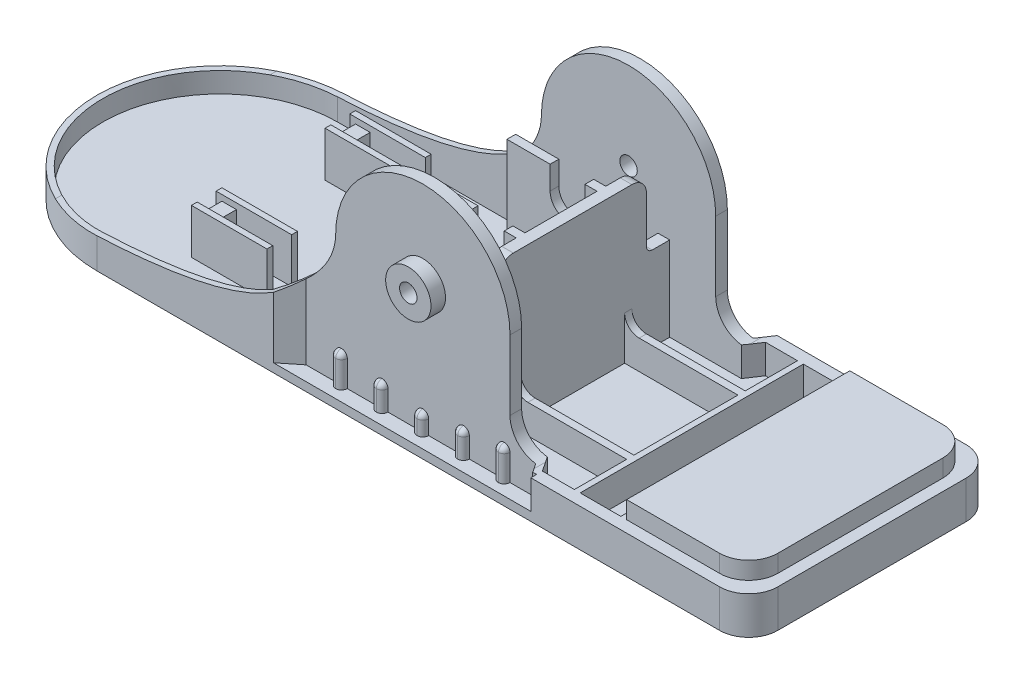
SolidWorks part; units mm, degrees
ref_plane "Front Plane" through (0, 0, 0) normal (0, 0, 1) x (1, 0, 0)
ref_plane "Top Plane" through (0, 0, 0) normal (0, 1, 0) x (1, 0, 0)
ref_plane "Right Plane" through (0, 0, 0) normal (1, 0, 0) x (0, 0, -1)
sketch "Sketch1" plane through (0, 0, 0) normal (0, 1, 0) x (1, 0, 0)
  line L0 (-66.675, 0) -> (-45.475, 0)
  line L1 (-45.475, -21.2) -> (66.675, -21.2)
  line L2 (-66.675, -21.2) -> (-66.675, 0) construction
  line L3 (-45.475, 21.2) -> (66.675, 21.2)
  line L4 (66.675, -21.2) -> (66.675, 21.2)
  line L5 (-66.675, -21.2) -> (66.675, 21.2) construction
  line L6 (-66.675, 21.2) -> (66.675, -21.2) construction
  line L7 (-66.675, 0) -> (-66.675, 21.2) construction
  line L8 (-66.675, 21.2) -> (-45.475, 21.2) construction
  line L9 (-66.675, -21.2) -> (-45.475, -21.2) construction
  arc A0 (-45.475, 21.2) -> (-45.475, -21.2) centre (-45.475, 0) ccw
  arc A1 (-45.475, -21.2) -> (-25.946, -8.2498) centre (-45.475, 0) ccw construction
  arc A2 (-25.946, -8.2498) -> (-25.946, 8.2498) centre (-45.475, 0) ccw construction
  arc A3 (-25.946, 8.2498) -> (-45.475, 21.2) centre (-45.475, 0) ccw construction
  point P0 (0, 0)
  dimension "D1" = 133.35
  dimension "D2" = 42.4
  dimension "D3" = 21.2
extrude "Boss-Extrude1" add sketch "Sketch1" along normal blind 1.5 contours L3 L4 L1 A0
fillet "Fillet1" radius 5 2 edges at (66.675, 0.75, -21.2) (66.675, 0.75, 21.2)
sketch "Sketch3" plane through (0, 1.5, 0) normal (0, 1, 0) x (1, 0, 0)
  line L0 (66.675, -21.2) -> (29.175, -21.2)
  line L1 (-45.475, -21.2) -> (61.675, -21.2) construction
  line L2 (29.175, -21.2) -> (29.175, 21.2)
  line L3 (-45.475, 21.2) -> (61.675, 21.2) construction
  line L4 (29.175, 21.2) -> (66.675, 21.2)
  line L5 (66.675, 21.2) -> (66.675, -21.2)
  line L6 (59.675, -19.2) -> (31.175, -19.2)
  line L8 (31.175, 19.2) -> (59.675, 19.2)
  line L9 (64.675, 14.2) -> (64.675, -14.2)
  line L10 (31.175, 19.2) -> (64.675, 19.2) construction
  line L11 (64.675, 19.2) -> (64.675, -19.2) construction
  line L12 (64.675, -19.2) -> (31.175, -19.2) construction
  line L13 (64.675, -19.2) -> (35.675, -19.2)
  line L14 (31.175, -19.2) -> (29.175, -19.2)
  line L15 (35.675, -19.2) -> (34.675, -19.2)
  line L16 (35.675, -19.2) -> (35.675, 19.2)
  line L17 (35.675, 19.2) -> (34.675, 19.2)
  line L18 (34.675, -19.2) -> (34.675, 19.2)
  line L19 (31.175, 19.2) -> (29.175, 19.2)
  line L20 (64.675, -0.7956) -> (43.675, -0.7956) construction
  line L21 (31.175, -19.2) -> (31.175, 19.2) construction
  line L23 (43.675, 19.2) -> (42.675, 19.2)
  line L24 (43.675, 19.2) -> (43.675, -19.2)
  line L25 (43.675, -19.2) -> (42.675, -19.2)
  line L26 (42.675, 19.2) -> (42.675, -19.2)
  arc A0 (59.675, 19.2) -> (64.675, 14.2) centre (59.675, 14.2) cw
  arc A1 (59.675, -19.2) -> (64.675, -14.2) centre (59.675, -14.2) ccw
  line M21 (66.675, -16.2) -> (66.675, 16.2)
  arc M22 (66.675, 16.2) -> (61.675, 21.2) centre (61.675, 16.2) ccw
  line M23 (61.675, 21.2) -> (-45.475, 21.2)
  line M25 (-45.475, -21.2) -> (61.675, -21.2)
  arc M26 (61.675, -21.2) -> (66.675, -16.2) centre (61.675, -16.2) ccw
  dimension "D3" = 5
  dimension "D1" = 37.5
  dimension "D4" = 29
  dimension "D5" = 1
  dimension "D6" = 0
  dimension "D7" = 21
  dimension "D8" = 1
  dimension "D2" = 2
extrude "Boss-Extrude2" add sketch "Sketch3" along normal blind 5 contours A1 L6 L13 L14 L2 L19 L8 A0 L9 M25 M26 M21 M22 M23 | L26 L25 L24 L23 | L16 L17 L18 L15 region at (45.425, 1.5, 20.634)
extrude "Boss-Extrude3" add sketch "Sketch3<3>" along normal blind 8 separate body contours L6 A1 L9 A0 L8 L24 region at (54.0485, 1.5, 0)
sketch "Sketch3<3>" plane through (0, 1.5, 0) normal (0, 1, 0) x (1, 0, 0) same geometry as "Sketch3"
sketch "Sketch6" plane through (0, 1.5, 0) normal (0, 1, 0) x (1, 0, 0)
  line L0 (29.175, -21.2) -> (27.5167, -18.7)
  line L1 (29.175, -21.2) -> (61.675, -21.2) construction
  line L2 (29.175, -19.2) -> (27.5167, -16.7)
  line L3 (-45.475, -21.2) -> (29.175, -21.2) construction
  line L4 (27.5167, -18.7) -> (-11.9833, -18.7)
  line L5 (27.5167, -16.7) -> (-11.9833, -16.7)
  line L6 (-11.9833, -18.7) -> (-15.1058, -21.2)
  line L7 (-11.9833, -16.7) -> (-16.3548, -20.2)
  line L8 (-45.475, 21.2) -> (29.175, 21.2) construction
  line L9 (-45.475, 21.2) -> (-16.3548, 21.2)
  line L10 (28.5117, -20.2) -> (29.175, -20.2)
  line L11 (-45.475, -20.2) -> (29.175, -20.2)
  line L12 (-45.475, -20.2) -> (-16.3548, -20.2)
  line L13 (-16.3548, -20.2) -> (-13.8568, -20.2) construction
  line L14 (-13.8568, -20.2) -> (28.5117, -20.2) construction
  line L15 (-45.475, -21.2) -> (-16.3548, -21.2)
  line L16 (27.5167, 16.7) -> (-11.9833, 16.7)
  line L17 (-16.3548, 21.2) -> (-15.1058, 21.2)
  line L18 (-16.3548, -21.2) -> (-15.1058, -21.2)
  line L19 (29.175, -19.2) -> (29.175, -21.2)
  line L20 (-45.475, 20.2) -> (-16.3548, 20.2)
  line L21 (-11.9833, 16.7) -> (-16.3548, 20.2)
  line L22 (-11.9833, 18.7) -> (-15.1058, 21.2)
  line L23 (27.5167, 18.7) -> (-11.9833, 18.7)
  line L24 (29.175, 19.2) -> (27.5167, 16.7)
  line L25 (29.175, 21.2) -> (27.5167, 18.7)
  line L26 (29.175, 19.2) -> (29.175, 21.2)
  arc A0 (-45.475, 21.2) -> (-45.475, -21.2) centre (-45.475, 0) ccw
  arc A4 (-45.475, 20.2) -> (-45.475, -20.2) centre (-45.475, 0) ccw
  arc A5 (-45.475, 20.2) -> (-45.475, -20.2) centre (-45.475, 0) ccw
  point P16 (0, 0)
  line M22 (29.175, 19.2) -> (29.175, 21.2)
  line M23 (29.175, 21.2) -> (-45.475, 21.2)
  arc M24 (-45.475, 21.2) -> (-45.475, -21.2) centre (-45.475, 0) ccw
  line M25 (-45.475, -21.2) -> (29.175, -21.2)
  line M26 (29.175, -21.2) -> (29.175, -19.2)
  dimension "D1" = 2.5
  dimension "D2" = 3
  dimension "D3" = 39.5
  dimension "D4" = 2.5
  dimension "D5" = 2
  dimension "D6" = 4
  dimension "D7" = 2.5
  dimension "D9" = 3
  dimension "D10" = 2.5
  dimension "D8" = 1
  dimension "D11" = 1
extrude "Boss-Extrude4" add sketch "Sketch6" along normal blind 37 contours A5 L20 L21 L16 L24 L25 L23 L22 L6 L4 L0 L10 L2 L5 L7 L12 M22 M23 M24 M25 M26 region at (6.9463, 1.5, 17.8201) region at (-15.7303, 1.5, 21.0952)
sketch "Sketch9" plane through (0, 0, 21.2) normal (0, 0, 1) x (1, 0, 0)
  line L0 (-66.675, 38.5) -> (-45.475, 38.5)
  line L1 (8.1, 0) -> (8.1, 23.5)
  line L2 (-45.475, 0) -> (61.675, 0) construction
  line L3 (8.1, 0) -> (-141.45, 0)
  line L4 (-66.675, 0) -> (-66.675, 5)
  line L5 (-66.675, 5) -> (-13.2209, 5) construction
  line L6 (-66.675, 5) -> (-66.675, 38.5)
  line L7 (8.1, 38.5) -> (-66.675, 38.5)
  line L8 (29.175, 6.5) -> (23.1, 23.5)
  line L9 (23.1, 23.5) -> (23.1, 11.5)
  line L10 (28.1, 6.5) -> (29.175, 6.5)
  line L11 (8.1, 38.5) -> (29.175, 38.5)
  line L12 (29.175, 38.5) -> (29.175, 6.5)
  circle A0 centre (8.1, 23.5) radius 15
  arc A1 (23.1, 11.5) -> (28.1, 6.5) centre (28.1, 11.5) ccw
  spline S0 degree 3 poles (-6.9, 23.5) (-6.9, 19.2277) (-18.2844, 4.0271) (-52.7634, 5) (-66.675, 5) knots 0 0 0 0 0.343246 1 1 1 1
  line M10 (-15.1058, 1.5) -> (-15.1058, 38.5)
  line M11 (-15.1058, 38.5) -> (-45.475, 38.5)
  line M12 (-45.475, 38.5) -> (-45.475, 0)
  dimension "D2" = 30
  dimension "D4" = 5
  dimension "D1" = 23.5
  dimension "D3" = 5
extrude "Cut-Extrude1" cut sketch "Sketch9" against normal through all both and the other way through all contours S0 A0 L7 M10 | S0 M10 M11 M12 | L6 L5 S0 L0 M12 | A0 L8 L12 L11 | L9 A1 L10 L8 region at (-56.0848, 21.7705, 21.2) region at (-30.7898, 22.8769, 21.2) region at (-9.692, 28.6572, 21.2) region at (24.7967, 28.49, 21.2) region at (25.2303, 12.6942, 21.2)
sketch "Sketch10" plane through (0, 0, 0) normal (0, -1, 0) x (1, 0, 0)
  line L0 (-66.675, 0) -> (-56.675, 0) construction
  line L1 (-56.675, 0) -> (-45.475, 0) construction
  line L2 (-45.475, -11.2) -> (-45.475, 11.2)
  arc A0 (-45.475, 21.2) -> (-45.475, -21.2) centre (-45.475, 0) ccw construction
  arc A1 (-45.475, 11.2) -> (-45.475, -11.2) centre (-45.475, 0) ccw
  arc A2 (-45.475, -11.2) -> (-45.475, 11.2) centre (-45.475, 0) ccw construction
  point P11 (-45.475, 0)
  dimension "D1" = 22.4
extrude "Cut-Extrude2" cut sketch "Sketch10" against normal blind 0.5 contours L2 A1
sketch "Sketch11" plane through (0, 1.5, 0) normal (0, 1, 0) x (1, 0, 0)
  line L0 (29.175, 19.2) -> (29.175, 10.2) construction
  line L1 (34.675, 10.2) -> (15.175, 10.2)
  line L2 (34.675, -19.2) -> (34.675, 19.2) construction
  line L3 (29.175, -19.2) -> (29.175, -10.2) construction
  line L4 (34.675, -10.2) -> (15.175, -10.2)
  line L5 (15.175, -16.7) -> (15.175, 16.7)
  line L6 (27.5167, -16.7) -> (-11.9833, -16.7) construction
  line L7 (27.5167, 16.7) -> (-11.9833, 16.7) construction
  line L8 (23.1, -16.7) -> (-6.9, -16.7) construction
  line L9 (15.175, 16.7) -> (13.175, 16.7)
  line L10 (15.175, 16.7) -> (15.175, -16.7)
  line L11 (15.175, -16.7) -> (13.175, -16.7)
  line L12 (13.175, 16.7) -> (13.175, -16.7)
  line L13 (15.175, 10.2) -> (15.175, 8.95)
  line L14 (15.175, 8.95) -> (34.675, 8.95)
  line L15 (15.175, -10.2) -> (15.175, -8.95)
  line L16 (15.175, -8.95) -> (34.675, -8.95)
  line L17 (15.175, -16.7) -> (15.175, -12.7)
  line L18 (15.175, -12.7) -> (13.175, -12.7)
  line L19 (13.175, 16.7) -> (13.175, 7.7)
  line L20 (13.175, 7.7) -> (15.175, 7.7)
  line L21 (13.175, -16.7) -> (13.175, -7.7)
  line L22 (13.175, 16.7) -> (13.175, 7.7)
  line L24 (13.175, 7.7) -> (-2.325, 7.7)
  line L25 (13.175, 7.7) -> (13.175, 6.2)
  line L26 (13.175, 6.2) -> (-2.325, 6.2)
  line L27 (-2.325, 7.7) -> (-2.325, 6.2)
  line L28 (13.175, -7.7) -> (-2.325, -7.7)
  line L29 (13.175, -7.7) -> (13.175, -6.2)
  line L30 (13.175, -6.2) -> (-2.325, -6.2)
  line L31 (-2.325, -7.7) -> (-2.325, -6.2)
  line L32 (13.175, 16.7) -> (15.175, 16.7)
  line L33 (13.175, 16.7) -> (13.175, 12.7)
  line L34 (13.175, 12.7) -> (15.175, 12.7)
  line L35 (15.175, 16.7) -> (15.175, 12.7)
  line M9 (27.5167, 16.7) -> (-11.9833, 16.7)
  line M15 (-11.9833, -16.7) -> (27.5167, -16.7)
  line M18 (34.675, -19.2) -> (34.675, 19.2)
  dimension "D1" = 9
  dimension "D2" = 19.5
  dimension "D3" = 9
  dimension "D4" = 2
  dimension "D5" = 1.25
  dimension "D6" = 1.25
  dimension "D7" = 4
  dimension "D8" = 9
  dimension "D9" = 9
  dimension "D10" = 9
  dimension "D11" = 1.5
  dimension "D12" = 15.5
  dimension "D13" = 1.5
  dimension "D14" = 15.5
  dimension "D15" = 4
extrude "Boss-Extrude5" add sketch "Sketch11" along normal up to surface (5 mm away) contours L16 L5 L4 M18 | L5 L18 L12 M15 | L20 L12 L22 L18 L10 L5 | L31 L28 L12 L30 | L10 L14 L1 M18 | L12 L20 L10 M9 | L24 L27 L26 L12 | L34 L22 L20 L5 L10 region at (24.925, 1.5, -9.575) region at (14.175, 1.5, -10.2) region at (14.175, 1.5, -14.7) region at (24.925, 1.5, 9.575) region at (14.175, 1.5, 2.5) region at (5.425, 1.5, -6.95) region at (14.175, 1.5, 14.7) region at (5.425, 1.5, 6.95) up to face at (38.4317, 6.5, 2.4)
extrude "Boss-Extrude6" add sketch "Sketch11<6>" along normal blind 26 contours L34 L22 L20 L5 L10 | L20 L12 L18 L10 L5 | L28 L31 L30 L29 | L24 L27 L26 L25 region at (14.175, 1.5, 2.5) region at (14.175, 1.5, -10.2)
sketch "Sketch11<6>" plane through (0, 1.5, 0) normal (0, 1, 0) x (1, 0, 0) same geometry as "Sketch11"
extrude "Boss-Extrude7" add sketch "Sketch11<7>" along normal blind 14.5 contours L5 L18 L12 M15 | L12 L34 L10 M9 region at (14.175, 1.5, 14.7) region at (14.175, 1.5, -14.7)
sketch "Sketch11<7>" plane through (0, 1.5, 0) normal (0, 1, 0) x (1, 0, 0) same geometry as "Sketch11"
fillet "Fillet2" radius 2.5 2 edges at (15.175, 6.5, 9.575) (15.175, 6.5, -9.575)
fillet "Fillet3" radius 1 2 edges at (14.175, 16, -12.7) (14.175, 16, 12.7)
fillet "Fillet4" radius 2.5 2 edges at (14.175, 27.5, -12.7) (14.175, 27.5, 12.7)
sketch "Sketch13" plane through (0, 0, -18.7) normal (0, 0, -1) x (-1, 0, 0)
  line L0 (-8.1, 38.5) -> (-8.1, 23.5) construction
  arc A0 (6.9, 23.5) -> (-23.1, 23.5) centre (-8.1, 23.5) ccw construction
  circle A1 centre (-8.1, 23.5) radius 1.5
  circle A2 centre (-8.1, 23.5) radius 3.9
  dimension "D1" = 3
  dimension "D2" = 7.8
extrude "Cut-Extrude3" cut sketch "Sketch13" against normal through all both and the other way through all contours A1
extrude "Boss-Extrude9" add sketch "Sketch13<3>" along normal blind 2.5
sketch "Sketch13<3>" plane through (0, 0, -18.7) normal (0, 0, -1) x (-1, 0, 0) same geometry as "Sketch13"
sketch "Sketch15" plane through (0, 0, 18.7) normal (0, 0, 1) x (1, 0, 0)
  line L0 (8.1, 38.5) -> (8.1, 23.5)
  arc A0 (23.1, 23.5) -> (-6.9, 23.5) centre (8.1, 23.5) ccw construction
  circle A1 centre (8.1, 23.5) radius 3.9
  circle M2 centre (8.1, 23.5) radius 1.5
  dimension "D1" = 7.8
extrude "Boss-Extrude10" add sketch "Sketch15" along normal blind 2.5 contours A1 M2 region at (10.7797, 26.1797, 18.7)
sketch "Sketch16" plane through (0, 0, 7.7) normal (0, 0, 1) x (1, 0, 0)
  line L0 (13.175, 27.5) -> (8.1, 23.5) construction
  line L1 (8.1, 23.5) -> (8.1, 27.5) construction
  line L2 (13.175, 27.5) -> (-2.325, 27.5) construction
  line L3 (5.1, 23.5) -> (5.1, 27.5)
  line L4 (11.1, 23.5) -> (11.1, 27.5)
  circle A0 centre (8.1, 23.5) radius 3
  point P12 (11.1, 27.5)
  circle M2 centre (8.1, 23.5) radius 1.5
  line M4 (13.175, 27.5) -> (-2.325, 27.5)
  dimension "D1" = 6
extrude "Cut-Extrude4" cut sketch "Sketch16" against normal up to surface (15.4 mm away) contours A0 L4 L3 M4 | A0 M2 region at (8.1, 26.5417, 7.7) region at (8.1, 26.4151, 7.7) up to face at (9.6, 23.5, -7.7)
sketch "Sketch18" plane through (0, 1.5, 0) normal (0, 1, 0) x (1, 0, 0)
  line L0 (-31.3725, 20.2) -> (-31.3725, 15.7)
  line L1 (-45.475, 20.2) -> (-16.3548, 20.2) construction
  line L2 (-37.8725, 15.7) -> (-24.8725, 15.7)
  line L3 (-37.8725, 15.7) -> (-37.8725, 14.7)
  line L4 (-37.8725, 14.7) -> (-24.8725, 14.7)
  line L5 (-24.8725, 14.7) -> (-24.8725, 15.7)
  line L6 (-36.8725, 14.7) -> (-34.3725, 14.7)
  line L7 (-37.8725, 14.7) -> (-36.8725, 14.7)
  line L8 (-37.8725, 14.7) -> (-37.8725, 11.45) construction
  line L9 (-37.8725, 11.45) -> (-36.8725, 11.45)
  line L10 (-36.8725, 14.7) -> (-36.8725, 11.45)
  line L11 (-34.3725, 14.7) -> (-34.3725, 11.45)
  line L12 (-34.3725, 11.45) -> (-24.8725, 11.45)
  line L13 (-24.8725, 11.45) -> (-24.8725, 10.45)
  line L14 (-24.8725, 10.45) -> (-37.8725, 10.45)
  line L15 (-37.8725, 10.45) -> (-37.8725, 11.45)
  line L16 (-36.8725, 13.075) -> (-60.8725, 13.075)
  line L17 (-36.8725, 11.45) -> (-34.3725, 11.45)
  line L18 (-31.3725, -12.55) -> (-31.3725, -20.2)
  line L19 (-37.8725, -7.3) -> (-24.8725, -7.3)
  line L20 (-37.8725, -7.3) -> (-37.8725, -8.3)
  line L21 (-37.8725, -8.3) -> (-24.8725, -8.3)
  line L22 (-24.8725, -8.3) -> (-24.8725, -7.3)
  line L23 (-36.8725, -8.3) -> (-34.3725, -8.3)
  line L24 (-37.8725, -8.3) -> (-36.8725, -8.3)
  line L25 (-37.8725, -8.3) -> (-37.8725, -11.55) construction
  line L26 (-37.8725, -11.55) -> (-36.8725, -11.55)
  line L27 (-36.8725, -8.3) -> (-36.8725, -11.55)
  line L28 (-34.3725, -8.3) -> (-34.3725, -11.55)
  line L29 (-34.3725, -11.55) -> (-24.8725, -11.55)
  line L30 (-24.8725, -11.55) -> (-24.8725, -12.55)
  line L31 (-24.8725, -12.55) -> (-37.8725, -12.55)
  line L32 (-37.8725, -12.55) -> (-37.8725, -11.55)
  line L33 (-45.475, -20.2) -> (-16.3548, -20.2) construction
  line L34 (-36.8725, -11.55) -> (-34.3725, -11.55)
  arc A0 (-45.475, 20.2) -> (-45.475, -20.2) centre (-45.475, 0) ccw construction
  point P6 (-31.3725, 15.7)
  point P26 (-31.3725, -7.3)
  dimension "D1" = 4.5
  dimension "D2" = 1
  dimension "D3" = 13
  dimension "D4" = 3.25
  dimension "D5" = 1
  dimension "D6" = 2.5
  dimension "D7" = 1
  dimension "D8" = 24
  dimension "D9" = 7.65
  dimension "D10" = 1
  dimension "D11" = 13
  dimension "D12" = 3.25
  dimension "D13" = 1
  dimension "D14" = 2.5
  dimension "D15" = 1
extrude "Boss-Extrude11" add sketch "Sketch18" along normal blind 7.75 contours L34 L26 L32 L31 L30 L29 | L21 L22 L19 L20 | L17 L9 L15 L14 L13 L12 | L4 L5 L2 L3 region at (-31.3725, 1.5, -15.2) region at (-31.3725, 1.5, -10.95) region at (-31.3725, 1.5, 7.8) region at (-31.3725, 1.5, 12.05)
extrude "Boss-Extrude12" add sketch "Sketch18<6>" along normal blind 6.75 contours L10 L17 L11 L4 | L27 L34 L28 L21 region at (-35.6225, 1.5, -13.075) region at (-35.6225, 1.5, 9.925)
sketch "Sketch18<6>" plane through (0, 1.5, 0) normal (0, 1, 0) x (1, 0, 0) same geometry as "Sketch18"
sketch "Sketch19" plane through (0, 0, 18.7) normal (0, 0, 1) x (1, 0, 0)
  line L0 (8.1, 23.5) -> (8.1, 1.5)
  line L1 (-15.1058, 1.5) -> (29.175, 1.5) construction
  line L2 (8.1, 1.5) -> (8.1, 5)
  line L3 (7.1, 5) -> (9.1, 5)
  line L4 (27.5167, 1.5) -> (-11.9833, 1.5) construction
  line L5 (9.1, 5) -> (7.1, 5)
  line L6 (9.1, 5) -> (9.1, 1.5)
  line L7 (9.1, 1.5) -> (7.1, 1.5)
  line L8 (7.1, 5) -> (7.1, 1.5)
  line L9 (9.1, 1.5) -> (14.1, 1.5)
  line L10 (16.1, 1.5) -> (21.1, 1.5)
  line L11 (14.1, 1.5) -> (16.1, 1.5)
  line L12 (14.1, 1.5) -> (14.1, 6)
  line L13 (14.1, 6) -> (16.1, 6)
  line L14 (16.1, 1.5) -> (16.1, 6)
  line L16 (21.1, 1.5) -> (23.1, 1.5)
  line L17 (21.1, 1.5) -> (21.1, 7)
  line L18 (21.1, 7) -> (23.1, 7)
  line L19 (23.1, 1.5) -> (23.1, 7)
  line L21 (2.1, 1.5) -> (2.1, 6)
  line L28 (2.1, 1.5) -> (0.1, 1.5)
  line L29 (-6.9, 1.5) -> (-6.9, 7)
  line L30 (-4.9, 7) -> (-6.9, 7)
  line L31 (-4.9, 1.5) -> (-4.9, 7)
  line L32 (-4.9, 1.5) -> (-6.9, 1.5)
  line L33 (0.1, 1.5) -> (0.1, 6)
  line L34 (2.1, 6) -> (0.1, 6)
  line L35 (0.1, 1.5) -> (-4.9, 1.5)
  point P9 (8.1, 5)
  point P22 (0, 0)
  point P24 (0, 0)
  point P25 (0, 0)
  line M18 (-11.9833, 1.5) -> (27.5167, 1.5)
  dimension "D1" = 3.5
  dimension "D2" = 2
  dimension "D3" = 5
  dimension "D4" = 2
  dimension "D5" = 4.5
  dimension "D6" = 5
  dimension "D7" = 2
  dimension "D8" = 5.5
  dimension "D9" = 5
  dimension "D10" = 2
  dimension "D11" = 2
  dimension "D12" = 5.5
  dimension "D13" = 4.5
  dimension "D14" = 5
sketch "Sketch20" plane through (0, 0, -18.7) normal (0, 0, -1) x (-1, 0, 0)
  line L0 (-8.1, 23.5) -> (-8.1, 1.5)
  line L1 (-8.1, 1.5) -> (-8.1, 5)
  line L2 (-9.1, 5) -> (-7.1, 5)
  line L3 (-7.1, 5) -> (-9.1, 5)
  line L4 (-7.1, 5) -> (-7.1, 1.5)
  line L5 (-7.1, 1.5) -> (-9.1, 1.5)
  line L6 (-9.1, 5) -> (-9.1, 1.5)
  line L7 (-7.1, 1.5) -> (-2.1, 1.5)
  line L8 (-0.1, 1.5) -> (4.9, 1.5)
  line L9 (-2.1, 1.5) -> (-0.1, 1.5)
  line L10 (-2.1, 1.5) -> (-2.1, 6)
  line L11 (-2.1, 6) -> (-0.1, 6)
  line L12 (-0.1, 1.5) -> (-0.1, 6)
  line L13 (4.9, 1.5) -> (6.9, 1.5)
  line L14 (4.9, 1.5) -> (4.9, 7)
  line L15 (4.9, 7) -> (6.9, 7)
  line L16 (6.9, 1.5) -> (6.9, 7)
  line L17 (-14.1, 1.5) -> (-14.1, 6)
  line L18 (-14.1, 1.5) -> (-16.1, 1.5)
  line L19 (-23.1, 1.5) -> (-23.1, 7)
  line L20 (-21.1, 7) -> (-23.1, 7)
  line L21 (-21.1, 1.5) -> (-21.1, 7)
  line L22 (-21.1, 1.5) -> (-23.1, 1.5)
  line L23 (-16.1, 1.5) -> (-16.1, 6)
  line L24 (-14.1, 6) -> (-16.1, 6)
  line L25 (-16.1, 1.5) -> (-21.1, 1.5)
  line L26 (-27.5167, 1.5) -> (11.9833, 1.5) construction
  point P6 (-8.1, 5)
  point P24 (0, 0)
  point P26 (0, 0)
  point P29 (0, 0)
  point P30 (0, 0)
  point P31 (0, 0)
  point P32 (0, 0)
  point P33 (6.7599, 5.8249)
  line M20 (-27.5167, 1.5) -> (11.9833, 1.5)
  dimension "D1" = 3.5
  dimension "D2" = 2
  dimension "D3" = 5
  dimension "D4" = 2
  dimension "D5" = 4.5
  dimension "D6" = 5
  dimension "D7" = 2
  dimension "D8" = 5.5
  dimension "D9" = 5
  dimension "D10" = 2
  dimension "D11" = 2
  dimension "D12" = 5.5
  dimension "D13" = 4.5
  dimension "D14" = 5
extrude "Boss-Extrude13" add sketch "Sketch19" along normal blind 1 contours L31 L30 L29 M18 | L21 L34 L33 M18 | L6 L3 L0 M18 | L3 L8 L0 M18 | L14 L13 L12 M18 | L19 L18 L17 M18 region at (8.6, 3.25, 18.7) region at (7.6, 3.25, 18.7) region at (22.1, 4.25, 18.7) region at (15.1, 3.75, 18.7) region at (-5.9, 4.25, 18.7) region at (1.1, 3.75, 18.7)
fillet "Fillet5" radius 1 25 edges at (23.1, 7, 19.2) (21.1, 7, 19.2) (22.1, 7, 19.7) (16.1, 6, 19.2) (15.1, 6, 19.7) (14.1, 6, 19.2) (9.1, 5, 19.2) (7.1, 5, 19.2) (8.1, 5, 19.7) (-5.9, 7, 19.7) (1.1, 6, 19.7) (2.1, 6, 19.2) (0.1, 6, 19.2) (-4.9, 7, 19.2) (-6.9, 7, 19.2) (21.1, 4.25, 19.7) (23.1, 4.25, 19.7) (16.1, 3.75, 19.7) (14.1, 3.75, 19.7) (7.1, 3.25, 19.7) (9.1, 3.25, 19.7) (0.1, 3.75, 19.7) (2.1, 3.75, 19.7) (-6.9, 4.25, 19.7) (-4.9, 4.25, 19.7)
extrude "Boss-Extrude14" add sketch "Sketch20" along normal blind 1 contours L21 L20 L19 M20 | L17 L24 L23 M20 | L4 L2 L0 M20 | L2 L6 L0 M20 | L12 L11 L10 M20 | L16 L15 L14 M20 region at (7.6, 3.25, -18.7) region at (8.6, 3.25, -18.7) region at (-5.9, 4.25, -18.7) region at (1.1, 3.75, -18.7) region at (22.1, 4.25, -18.7) region at (15.1, 3.75, -18.7)
fillet "Fillet6" radius 1 25 edges at (-4.9, 7, -19.2) (-5.9, 7, -19.7) (-6.9, 7, -19.2) (2.1, 6, -19.2) (1.1, 6, -19.7) (0.1, 6, -19.2) (9.1, 5, -19.2) (8.1, 5, -19.7) (7.1, 5, -19.2) (16.1, 6, -19.2) (15.1, 6, -19.7) (14.1, 6, -19.2) (23.1, 7, -19.2) (22.1, 7, -19.7) (21.1, 7, -19.2) (-4.9, 4.25, -19.7) (-6.9, 4.25, -19.7) (2.1, 3.75, -19.7) (0.1, 3.75, -19.7) (9.1, 3.25, -19.7) (7.1, 3.25, -19.7) (16.1, 3.75, -19.7) (14.1, 3.75, -19.7) (23.1, 4.25, -19.7) (21.1, 4.25, -19.7)
